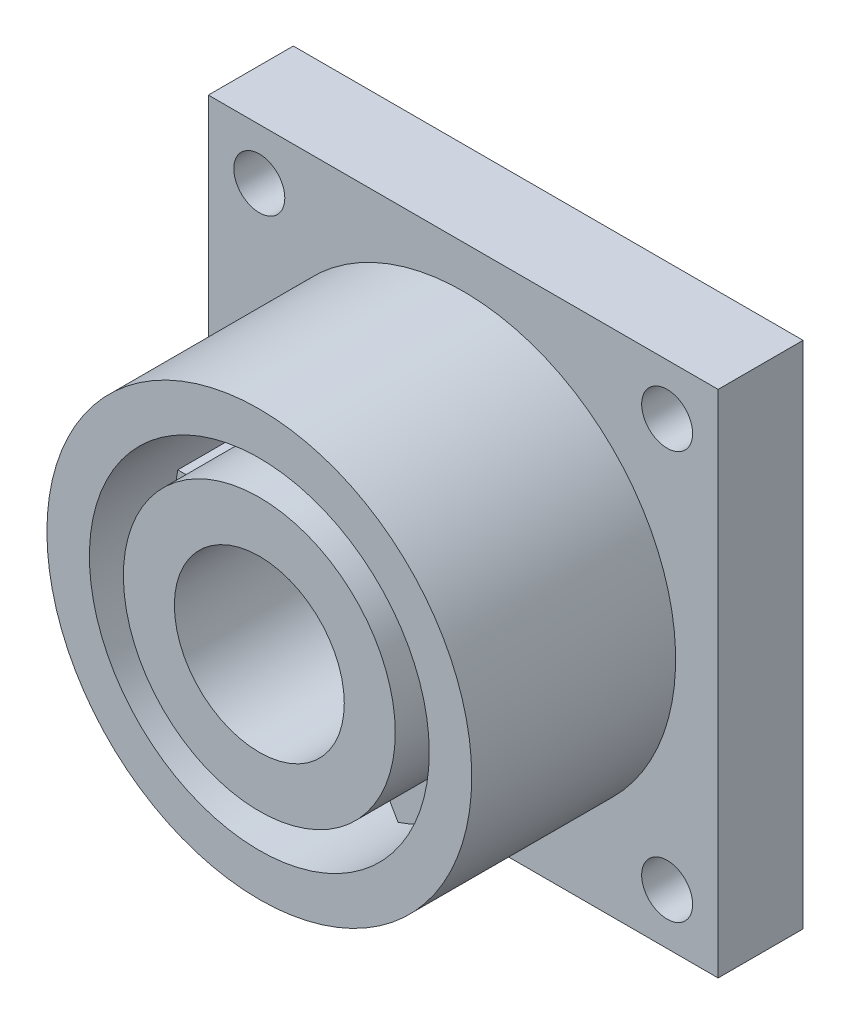
SolidWorks part; units mm, degrees
ref_plane "Alzado" through (0, 0, 0) normal (0, 0, 1) x (1, 0, 0)
ref_plane "Planta" through (0, 0, 0) normal (0, 1, 0) x (1, 0, 0)
ref_plane "Vista lateral" through (0, 0, 0) normal (1, 0, 0) x (0, 0, -1)
sketch "Croquis1" plane through (0, 0, 0) normal (0, 0, 1) x (1, 0, 0)
  line L0 (-12, 12) -> (12, 12) construction
  line L1 (-15, -15) -> (15, -15)
  line L2 (-15, -15) -> (-15, 15)
  line L3 (-15, 15) -> (15, 15)
  line L4 (15, -15) -> (15, 15)
  line L5 (-15, -15) -> (15, 15) construction
  line L6 (-15, 15) -> (15, -15) construction
  line L7 (-12, 12) -> (-12, -12) construction
  circle A0 centre (-12, 12) radius 1.5
  circle A1 centre (12, 12) radius 1.5
  circle A2 centre (12, -12) radius 1.5
  circle A3 centre (-12, -12) radius 1.5
  point P0 (0, 0)
  point P8 (0, 0)
  dimension "D3" = 3
  dimension "D5" = 2
  dimension "D1" = 30
  dimension "D2" = 30
  dimension "D4" = 3
  dimension "D7" = 24
  dimension "D8" = 24
  dimension "D6" = 2
extrude "Saliente-Extruir1" add sketch "Croquis1" along normal mid plane 5
sketch "Croquis2" plane through (0, 0, 2.5) normal (0, 0, 1) x (1, 0, 0)
  line L0 (-9.798, -2) -> (-7.746, -2)
  line L1 (-5, -8.6603) -> (5, 8.6603) construction
  line L8 (-5, 8.6603) -> (5, -8.6603) construction
  line L9 (-18.4242, 0) -> (18.4242, 0) construction
  line L10 (-9.798, 2) -> (-7.746, 2)
  line L11 (-3.1669, 9.4853) -> (-2.1409, 7.7082)
  line L12 (-6.631, 7.4853) -> (-5.605, 5.7082)
  line L13 (6.631, 7.4853) -> (5.605, 5.7082)
  line L14 (3.1669, 9.4853) -> (2.1409, 7.7082)
  line L15 (9.798, -2) -> (7.746, -2)
  line L16 (9.798, 2) -> (7.746, 2)
  line L17 (3.1669, -9.4853) -> (2.1409, -7.7082)
  line L18 (6.631, -7.4853) -> (5.605, -5.7082)
  line L19 (-6.631, -7.4853) -> (-5.605, -5.7082)
  line L20 (-3.1669, -9.4853) -> (-2.1409, -7.7082)
  line L21 (0, 0) -> (-7.746, 2) construction
  line L22 (0, 0) -> (-2.1409, 7.7082) construction
  circle A0 centre (0, 0) radius 10
  circle A1 centre (0, 0) radius 12.5
  circle A2 centre (0, 0) radius 8
  circle A3 centre (0, 0) radius 5
  dimension "D1" = 20
  dimension "D3" = 16
  dimension "D4" = 60
  dimension "D10" = 10
  dimension "D5" = 60
  dimension "D6" = 2
  dimension "D7" = 6
  dimension "D8" = 60
  dimension "D9" = 8
  dimension "D2" = 2.5
extrude "Saliente-Extruir2" add sketch "Croquis2" along normal blind 7 contours A2 L11 A0 L12 | A2 L13 A0 L14 | A2 L15 A0 L16 | A2 L17 A0 L18 | A2 L19 A0 L20 | A2 L10 A0 L0 | A1 A0 | A2 A3 region at (-8.9239, 0, 2.5) region at (-7.7737, 0, 2.5) region at (-4.4619, -7.7283, 2.5) region at (-4.4619, 7.7283, 2.5) region at (4.4619, -7.7283, 2.5) region at (4.4619, 7.7283, 2.5) region at (8.9239, 0, 2.5) region at (-12.1464, 0, 2.5)
sketch "Croquis4" plane through (0, 0, 9.5) normal (0, 0, 1) x (1, 0, 0)
  circle A0 centre (0, 0) radius 12.5 construction
  circle A1 centre (0, 0) radius 5
  circle A2 centre (0, 0) radius 5
  circle A3 centre (0, 0) radius 12.5
  circle A4 centre (0, 0) radius 10
  circle A7 centre (0, 0) radius 8
  circle A8 centre (0, 0) radius 8
  arc M4 (-7.746, -2) -> (-5.605, -5.7082) centre (0, 0) ccw
  arc M6 (-6.631, -7.4853) -> (-9.798, -2) centre (0, 0) cw
  arc M8 (-2.1409, -7.7082) -> (2.1409, -7.7082) centre (0, 0) ccw
  arc M10 (3.1669, -9.4853) -> (-3.1669, -9.4853) centre (0, 0) cw
  arc M12 (5.605, -5.7082) -> (7.746, -2) centre (0, 0) ccw
  arc M14 (9.798, -2) -> (6.631, -7.4853) centre (0, 0) cw
  arc M16 (7.746, 2) -> (5.605, 5.7082) centre (0, 0) ccw
  arc M18 (6.631, 7.4853) -> (9.798, 2) centre (0, 0) cw
  arc M20 (2.1409, 7.7082) -> (-2.1409, 7.7082) centre (0, 0) ccw
  arc M22 (-3.1669, 9.4853) -> (3.1669, 9.4853) centre (0, 0) cw
  arc M24 (-5.605, 5.7082) -> (-7.746, 2) centre (0, 0) ccw
  arc M26 (-9.798, 2) -> (-6.631, 7.4853) centre (0, 0) cw
  circle M27 centre (0, 0) radius 12.5
  circle M28 centre (0, 0) radius 5
  dimension "D1" = 0
  dimension "D2" = 2.5
  dimension "D3" = 3
extrude "Saliente-Extruir3" add sketch "Croquis4" along normal blind 5 contours A4 M27 M18 M14 M10 M6 M26 M22 | A8 M16 M20 M24 M4 M8 M12 M28 region at (-12.1464, 0, 9.5) region at (7.7118, -0.9795, 9.5)
